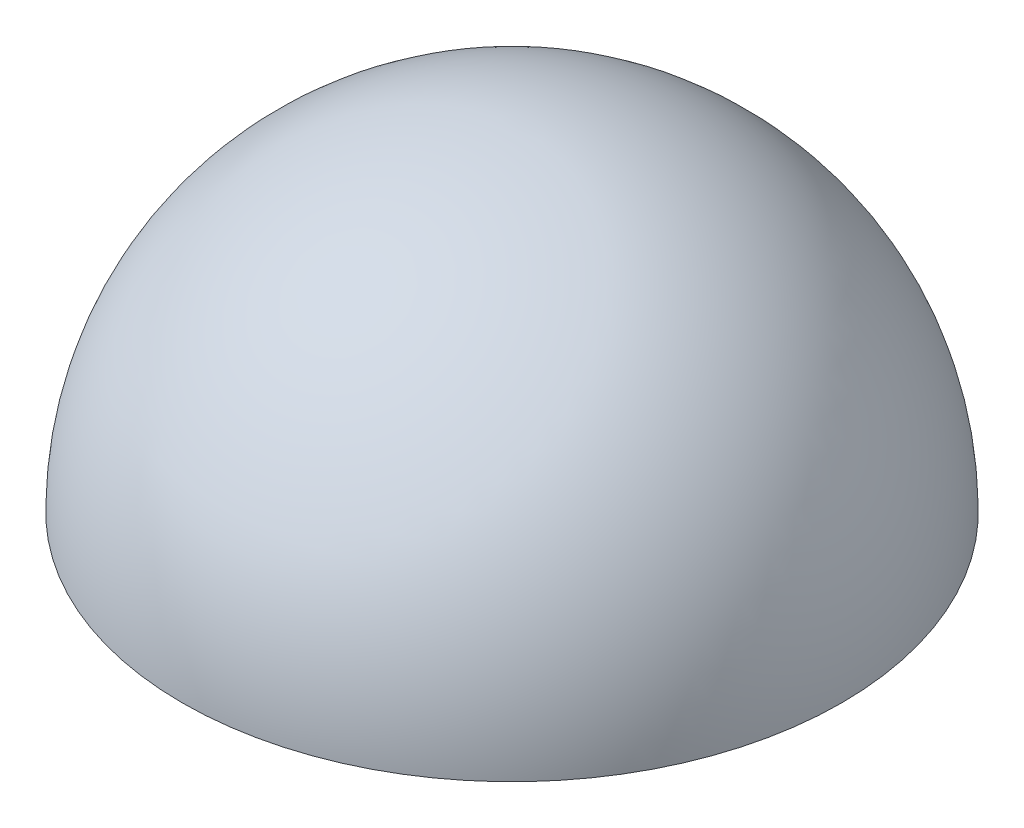
SolidWorks part; units mm, degrees
ref_plane "Front Plane" through (0, 0, 0) normal (0, 0, 1) x (1, 0, 0)
ref_plane "Top Plane" through (0, 0, 0) normal (0, 1, 0) x (1, 0, 0)
ref_plane "Right Plane" through (0, 0, 0) normal (1, 0, 0) x (0, 0, -1)
sketch "Sketch1" plane through (0, 0, 0) normal (0, 0, 1) x (1, 0, 0)
  line L0 (0, 10) -> (0, 0)
  line L1 (-9.6455, 0) -> (13.5037, 0) construction
  line L2 (55, 0) -> (-55, 0) construction
  line L3 (10, 0) -> (0, 0)
  arc A0 (10, 0) -> (0, 10) centre (0, 0) ccw
  dimension "D1" = 20
ref_axis "Axis1" through (0, -11, 0) along (0, 1, 0)
revolve "Revolve3" add sketch "Sketch1" angle 360 about L0
ref_plane "Plane1" through (0, 10, 0) normal (0, 1, 0) x (1, 0, 0)
